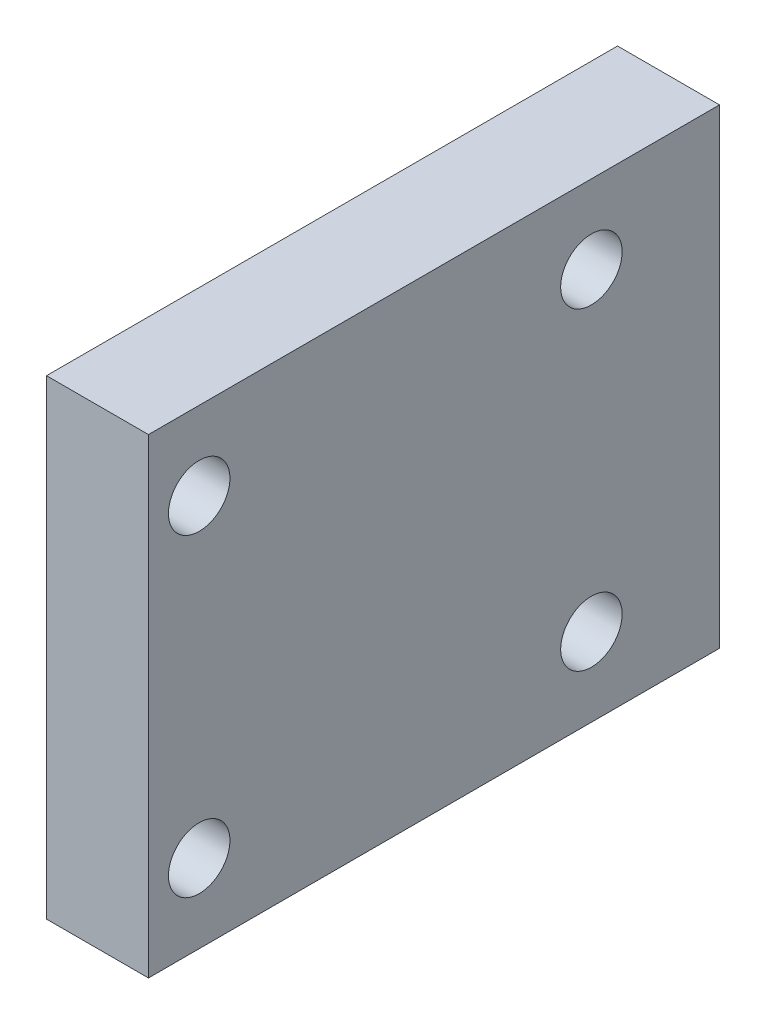
SolidWorks part; units mm, degrees
ref_plane "Front Plane" through (0, 0, 0) normal (0, 0, 1) x (1, 0, 0)
ref_plane "Top Plane" through (0, 0, 0) normal (0, 1, 0) x (1, 0, 0)
ref_plane "Right Plane" through (0, 0, 0) normal (1, 0, 0) x (0, 0, -1)
sketch "Sketch2" plane through (-488.9654, 0, 0) normal (1, 0, 0) x (0, 0, -1)
  line L1 (194.9873, 128.4838) -> (194.9873, 166.5838)
  line L2 (194.9873, 126.5338) -> (194.9873, 131.5338) construction
  line L3 (210.0161, 128.4838) -> (140.1661, 128.4838) construction
  line L4 (194.9873, 167.5338) -> (194.9873, 165.7338) construction
  line L5 (140.1661, 166.5838) -> (210.0161, 166.5838) construction
  line L6 (194.9873, 166.5838) -> (148.7593, 166.5838)
  line L7 (148.7593, 166.5838) -> (148.7593, 128.4838)
  line L8 (194.9873, 128.4838) -> (148.7593, 128.4838)
  dimension "D1" = 46.228
extrude "Boss-Extrude1" add sketch "Sketch2" along normal blind 8.255
hole_wizard "#10 Clearance Hole1" positions "Sketch3" profile "Sketch4" hole size "#10" standard "ANSI Inch"
sketch "Sketch3" plane through (-488.9654, 0, 0) normal (-1, 0, 0) x (0, 0, 1)
  point P0 (-184.6161, 160.2338)
  point P3 (-152.8661, 160.2338)
  point P6 (-152.8661, 134.8338)
  point P9 (-184.6161, 134.8338)
  point P15 (0, 0)
sketch "Sketch4" plane through (-488.9654, 160.2338, -184.6161) normal (0, 1, 0) x (0, 0, 1)
  line L0 (0, 0) -> (0, 26.8957)
  line L1 (0, 26.8957) -> (2.4892, 25.4)
  line L2 (2.4892, 25.4) -> (2.4892, 0)
  line L5 (2.4892, 0) -> (0, 0)
  line L10 (0, 26.8957) -> (-2.4892, 25.4) construction
  line L11 (0, -6.35) -> (0, 107.95) construction
  dimension "Hole Dia." = 4.9784
  dimension "Hole Depth" = 25.4
  dimension "Drill Angle" = 118
